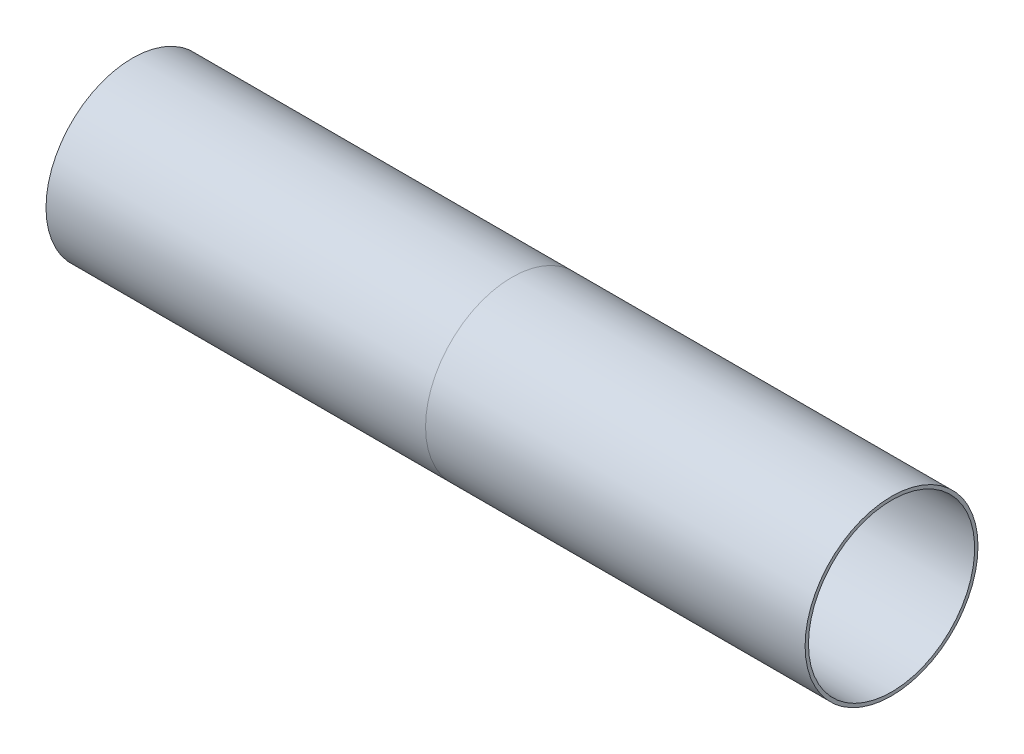
SolidWorks part; units mm, degrees
other "Coupler"
other "Middle Bit"
other "End Part"
ref_plane "Front Plane" through (0, 0, 0) normal (0, 0, 1) x (1, 0, 0)
ref_plane "Top Plane" through (0, 0, 0) normal (0, 1, 0) x (1, 0, 0)
ref_plane "Right Plane" through (0, 0, 0) normal (1, 0, 0) x (0, 0, -1)
sketch "Sketch2" plane through (0, 0, 0) normal (0, 1, 0) x (1, 0, 0)
  line L0 (0, 0) -> (180, 0)
  line L1 (180, 39.4) -> (180, 0) construction
  line L2 (0, 39.4) -> (0, 0) construction
  line L3 (180, 41) -> (0, 41)
  line L4 (180, 41) -> (180, 39.4)
  line L5 (180, 39.4) -> (0, 39.4)
  line L6 (0, 41) -> (0, 39.4)
  line L7 (90, 39.4) -> (90, 41) construction
  line L8 (180, 40.2) -> (0, 40.2) construction
  line L9 (0, 39.4) -> (28.6217, 37.9)
  line L10 (28.6217, 37.9) -> (30.1217, 39.4)
  line L11 (28.6217, 37.9) -> (28.6217, 39.4) construction
  line L12 (-30.1217, 39.4) -> (30.1217, 39.4)
  line L13 (0, 39.4) -> (-28.6217, 37.9)
  line L14 (-28.6217, 37.9) -> (-30.1217, 39.4)
  line L15 (-180, 39.4) -> (0, 39.4)
  line L16 (-180, 41) -> (0, 41)
  line L17 (-180, 41) -> (-180, 39.4)
  line L18 (-90, 41) -> (-90, 0) construction
  line L19 (-149.8783, 39.4) -> (-180, 39.4)
  line L20 (-151.3783, 37.9) -> (-149.8783, 39.4)
  line L21 (-180, 39.4) -> (-151.3783, 37.9)
  point P328 (90, 40.2)
  dimension "D1" = 180
  dimension "D2" = 41
  dimension "D3" = 1.6
  dimension "D4" = 45
  dimension "D5" = 3
  dimension "D6" = 1.5
revolve "Revolve1" add sketch "Sketch2" angle 360 about L0 region at (90, 0, -40.2) region at (19.5811, 0, -38.9)
revolve "Revolve2" add sketch "Sketch2<3>" angle 360 about L0 region at (-90, 0, -40.2) region at (-19.5811, 0, -38.9)
sketch "Sketch2<3>" plane through (0, 0, 0) normal (0, 1, 0) x (1, 0, 0) same geometry as "Sketch2"
sketch "Sketch3" plane through (0, 0, 0) normal (0, 1, 0) x (1, 0, 0)
  line L0 (-28.6217, 37.9) -> (0, 39.4)
  line L1 (0, 39.4) -> (28.6217, 37.9)
  line L2 (28.6217, 37.9) -> (28.6217, 36.7)
  line L3 (28.6217, 36.7) -> (-28.6217, 36.7)
  line L4 (-28.6217, 36.7) -> (-28.6217, 37.9)
  dimension "D1" = 1.2
revolve "Revolve3" add sketch "Sketch3" angle 360 about L0
